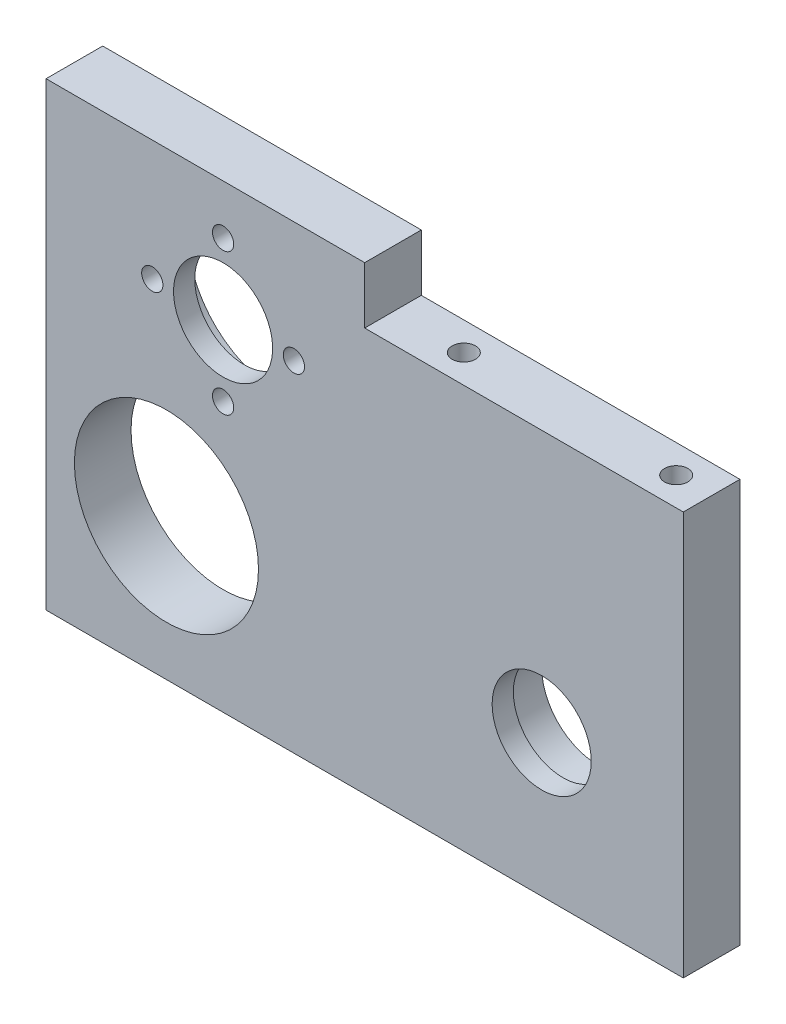
SolidWorks part; units mm, degrees
ref_plane "Front" through (0, 0, 0) normal (0, 0, 1) x (1, 0, 0)
ref_plane "Top" through (0, 0, 0) normal (0, 1, 0) x (1, 0, 0)
ref_plane "Right" through (0, 0, 0) normal (1, 0, 0) x (0, 0, -1)
sketch "Esquisse1" plane through (0, 0, 0) normal (0, 0, 1) x (1, 0, 0)
  line L1 (0, 0) -> (90, 0)
  line L2 (0, 0) -> (0, 65)
  line L3 (0, 65) -> (90, 65)
  line L4 (90, 0) -> (90, 65)
  circle A0 centre (70, 20) radius 7
  circle A1 centre (17, 20) radius 13
  circle A2 centre (25, 48) radius 13
  dimension "D3" = 14
  dimension "D4" = 20
  dimension "D6" = 53
  dimension "D8" = 26
  dimension "D9" = 26
  dimension "D1" = 90
  dimension "D2" = 65
  dimension "D5" = 70
  dimension "D7" = 20
  dimension "D10" = 53
  dimension "D11" = 48
extrude "Boss.-Extru.1" add sketch "Esquisse1" along normal blind 8
sketch "Esquisse2" plane through (0, 0, 0) normal (0, 0, -1) x (-1, 0, 0)
  circle A0 centre (-25, 48) radius 13
  circle A1 centre (-17, 20) radius 13 construction
extrude "Boss.-Extru.2" add sketch "Esquisse2" along normal blind 3 from surface starting at face at (45, 32.5, 8)
sketch "Esquisse3" plane through (0, 0, 5) normal (0, 0, -1) x (-1, 0, 0)
  line L0 (-15, 48) -> (-25, 48) construction
  circle A0 centre (-25, 48) radius 7
  circle A1 centre (-15, 48) radius 1.5
  circle A2 centre (-25, 38) radius 1.5
  circle A3 centre (-35, 48) radius 1.5
  circle A4 centre (-25, 58) radius 1.5
  point P13 (-25, 48)
  dimension "D1" = 14
  dimension "D2" = 3
  dimension "D3" = 10
  dimension "D4" = 4
extrude "Enlèv. mat.-Extru.1" cut sketch "Esquisse3" against normal through all
sketch "Esquisse4" plane through (0, 0, 8) normal (0, 0, 1) x (1, 0, 0)
  circle A0 centre (70, 20) radius 8
  dimension "D1" = 16
extrude "Enlèv. mat.-Extru.2" cut sketch "Esquisse4" along normal blind 5 from surface starting at face at (30, 20, 0)
sketch "Esquisse5" plane through (0, 0, 0) normal (0, 0, -1) x (-1, 0, 0)
  line L1 (-90, 65) -> (-45, 65)
  line L2 (-90, 65) -> (-90, 57)
  line L3 (-90, 57) -> (-45, 57)
  line L4 (-45, 65) -> (-45, 57)
  dimension "D1" = 8
  dimension "D2" = 45
extrude "Enlèv. mat.-Extru.3" cut sketch "Esquisse5" against normal through all
sketch "Esquisse6" plane through (0, 0, 0) normal (-1, 0, 0) x (0, 0, 1)
  line L0 (4, 0) -> (4, 35) construction
  line L1 (8, 0) -> (0, 0) construction
  circle A0 centre (4, 35) radius 1.65
  circle A1 centre (4, 7) radius 1.65
  dimension "D1" = 3.3
  dimension "D2" = 28
  dimension "D3" = 7
extrude "Enlèv. mat.-Extru.4" cut sketch "Esquisse6" against normal blind 10
sketch "Esquisse7" plane through (0, 57, 0) normal (0, 1, 0) x (1, 0, 0)
  line L0 (45, -4) -> (85, -4) construction
  line L1 (45, -8) -> (45, 0) construction
  circle A0 centre (85, -4) radius 1.65
  circle A1 centre (55, -4) radius 1.65
  dimension "D1" = 30
  dimension "D2" = 3.3
  dimension "D3" = 10
extrude "Enlèv. mat.-Extru.5" cut sketch "Esquisse7" against normal blind 10
